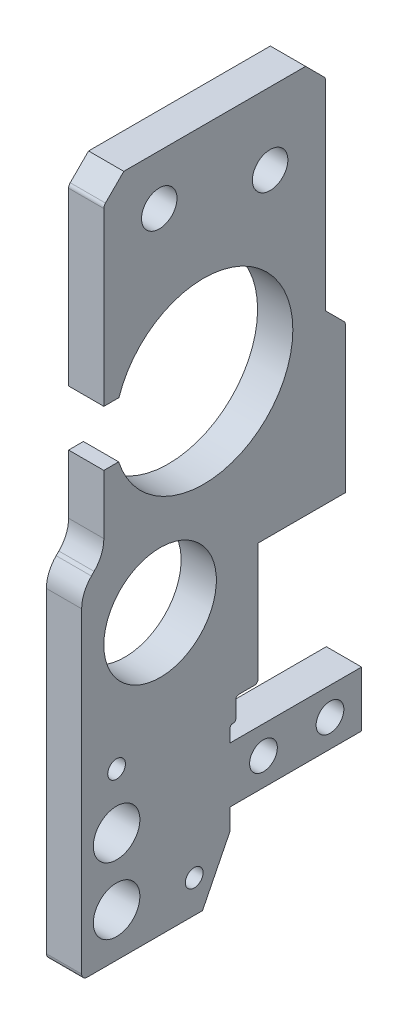
SolidWorks part; units mm, degrees
material "6061 Alloy"
ref_plane "Front Plane" through (0, 0, 0) normal (0, 0, 1) x (1, 0, 0)
ref_plane "Top Plane" through (0, 0, 0) normal (0, 1, 0) x (1, 0, 0)
ref_plane "Right Plane" through (0, 0, 0) normal (1, 0, 0) x (0, 0, -1)
sketch "Sketch1" plane through (0, 0, 0) normal (1, 0, 0) x (0, 0, -1)
  line L2 (0, 0) -> (0, 30.275)
  line L3 (0, 30.275) -> (2, 32.275)
  line L4 (2, 32.275) -> (2, 61.31)
  line L5 (2, 61.31) -> (22, 61.31)
  line L7 (23.8, 26.21) -> (15.9, 26.21)
  line L8 (13.4, 13.26) -> (13.4, 11.86)
  line L9 (13.4, 11.86) -> (25.25, 11.86)
  line L10 (25.25, 11.86) -> (25.25, 6.86)
  line L11 (25.25, 6.86) -> (13.4, 6.86)
  line L12 (13.4, 6.86) -> (13.4, 0)
  line L13 (13.4, 0) -> (0, 0)
  line L14 (-6.9356, -4) -> (62.4069, -4) construction
  line L15 (7.075, 30.275) -> (0, 30.275) construction
  line L16 (7.075, 20.125) -> (0, 20.125) construction
  line L17 (2, 18.125) -> (2, 32.275) construction
  line L18 (13.4, 13.26) -> (13.9, 13.26)
  line L19 (15.9, 15.26) -> (15.9, 26.21)
  line L23 (22, 61.31) -> (22, 41.31)
  line L24 (22, 41.31) -> (23.8, 41.31)
  line L25 (23.8, 41.31) -> (23.8, 26.21)
  line L29 (15.9, 15.26) -> (13.9, 15.26)
  line L30 (13.9, 13.26) -> (13.9, 15.26)
  circle A0 centre (7.075, 25.2) radius 5.075
  circle A1 centre (7, 56.81) radius 1.6
  circle A2 centre (17, 54.81) radius 1.6
  circle A3 centre (22.4, 9.36) radius 1.25
  circle A4 centre (16.4, 9.36) radius 1.25
  circle A5 centre (3.15, 3.95) radius 2.1
  circle A6 centre (3.15, 9.95) radius 2.1
  circle A7 centre (22.4, 9.36) radius 2.85 construction
  circle A8 centre (16.4, 9.36) radius 2.85 construction
  circle A9 centre (10.15, 2.95) radius 0.8
  circle A10 centre (3.15, 14.95) radius 0.8
  dimension "D11" = 10.15
  dimension "D13" = 3.2
  dimension "D17" = 5
  dimension "D21" = 2.5
  dimension "D29" = 7.9
  dimension "D33" = 4.2
  dimension "D34" = 5.7
  dimension "D35" = 2
  dimension "D36" = 1.6
  dimension "D3" = 10.86
  dimension "D4" = 5
  dimension "D5" = 14.35
  dimension "D6" = 11.85
  dimension "D7" = 61.31
  dimension "D8" = 4
  dimension "D9" = 2
  dimension "D10" = 2
  dimension "D12" = 29.2
  dimension "D14" = 6.5
  dimension "D15" = 4.5
  dimension "D16" = 5
  dimension "D18" = 6
  dimension "D19" = 1.45
  dimension "D20" = 2.5
  dimension "D22" = 1.4
  dimension "D23" = 7
  dimension "D24" = 20
  dimension "D25" = 2.95
  dimension "D26" = 1.8
  dimension "D27" = 20
  dimension "D28" = 2
  dimension "D30" = 6
  dimension "D31" = 3.95
  dimension "D32" = 3.15
  dimension "D38" = 12
extrude "Boss-Extrude1" add sketch "Sketch1" along normal blind 3.18
chamfer "Chamfer1" distance 2.5 angle 63.43 1 edges at (1.59, 0, -13.4) first distance on face at (1.59, 0, -6.7)
fillet "Fillet1" [suppressed] radius 1
sketch "Sketch3" [suppressed] plane through (0, 0, 0) normal (1, 0, 0) x (0, 0, -1)
  line L1 (-17.4326, 42.2448) -> (-6.9749, 46.4147) construction
  line L2 (-6.9749, 46.4147) -> (-8.5925, 35.2732) construction
  line L3 (-8.5925, 35.2732) -> (-17.4326, 42.2448) construction
  line L4 (-2, 61.31) -> (-2, 32.2) construction
  circle A0 centre (-11, 41.3109) radius 5
  circle A2 centre (-11, 41.3109) radius 6.5 construction
  circle A3 centre (-6.9749, 46.4147) radius 1.2 construction
  circle A4 centre (-8.5925, 35.2732) radius 1.2 construction
  circle A5 centre (-17.4326, 42.2448) radius 1.2 construction
  circle A6 centre (-7, 25.2) radius 5 construction
  dimension "D1" = 10
  dimension "D3" = 16.6
  dimension "D4" = 13
  dimension "D5" = 2.4
  dimension "D2" = 9
hole_wizard "CSK for M2 Flat Head Machine Screw1" [suppressed] positions "Sketch6" profile "Sketch7" countersink size "M2" standard "ANSI Metric"
sketch "Sketch6" plane through (0, 0, 0) normal (-1, 0, 0) x (0, 0, 1)
  point P0 (-6.9749, 46.4147)
  point P3 (-17.4326, 42.2448)
  point P6 (-8.5925, 35.2732)
sketch "Sketch7" plane through (0, 46.4147, -6.9749) normal (0, 1, 0) x (0, 0, 1)
  line L0 (0, 0) -> (0, 4.23)
  line L1 (0, 4.23) -> (1.2, 3.509)
  line L2 (1.2, 3.509) -> (1.2, 1)
  line L3 (1.2, 1) -> (2.2, 0)
  line L5 (2.2, 0) -> (0, 0)
  line L6 (-1.2, 1) -> (-2.2, 0) construction
  line L10 (0, 4.23) -> (-1.2, 3.509) construction
  line L11 (0, -6.35) -> (0, 107.95) construction
  dimension "Hole Dia." = 2.4
  dimension "Hole Depth" = 4.23
  dimension "Near C'Sink Dia." = 4.4
  dimension "Near C'Sink Angle" = 90
  dimension "Drill Angle" = 118
extrude "Cut-Extrude4" [suppressed] cut sketch "Sketch3" against normal through all
fillet "Fillet2" radius 3 2 edges at (1.59, 30.275, 0) (1.59, 32.275, -2)
fillet "Chamfer2" radius 1.8 3 edges at (1.59, 61.31, -22) (1.59, 61.31, -2) (1.59, 41.31, -23.8) profile chamfer
fillet "Fillet4" radius 0.5 5 edges at (1.59, 59.51, -2) (1.59, 59.51, -22) (1.59, 39.51, -23.8) (1.59, 0, 0) (1.59, 4.9989, -13.4)
fillet "Fillet6" [suppressed] radius 0.3
sketch "BallRef" [suppressed] plane through (0, 0, 0) normal (-1, 0, 0) x (0, 0, 1)
  line L0 (-31.524, -18.06) -> (65.6624, -18.06) construction
  line L1 (-0.75, 25.2) -> (-0.75, 21.8885) construction
  line L2 (-0.75, 21.8885) -> (31.3703, 21.8885) construction
  line L3 (31.3703, 3.35) -> (31.3703, 21.8885) construction
  line L4 (1.092, -18.06) -> (-13.908, -3.06) construction
  line L5 (-13.908, -3.06) -> (-13.908, -18.06) construction
  line L6 (-13.908, -18.06) -> (1.092, -18.06) construction
  circle A0 centre (-7, 25.2) radius 6.25 construction
  circle A1 centre (9.9603, 3.35) radius 21.41 construction
  dimension "D1" = 12.5
  dimension "D2" = 42.82
  dimension "D3" = 43.26
  dimension "D4" = 45
  dimension "D5" = 15
fillet "Fillet7" radius 0.2 2 edges at (1.59, 13.26, -13.4) (1.59, 13.26, -13.9)
hole_wizard "M3x0.5 Tapped Hole1" positions "Sketch9" profile "Sketch10" tap size "M3x0.5" standard "ANSI Metric" end condition through all
sketch "Sketch9" plane through (3.18, 0, 0) normal (1, 0, 0) x (0, 0, -1)
  point P0 (16.4, 9.36)
  point P3 (22.4, 9.36)
sketch "Sketch10" plane through (3.18, 9.36, -16.4) normal (0, 1, 0) x (0, 0, -1)
  line L0 (0, 0) -> (0, 3.18)
  line L1 (0, 3.18) -> (1.25, 3.18)
  line L2 (1.25, 3.18) -> (1.25, 0)
  line L5 (1.25, 0) -> (0, 0)
  line L11 (0, -6.35) -> (0, 107.95) construction
  dimension "Thru Tap Drill Dia." = 2.5
  dimension "Thru Tap Drill Depth" = 3.18
hole_wizard "M2 Tapped Hole1" positions "3DSketch1" profile "Sketch12" tap size "M2" standard "AS" end condition through all
sketch3d "3DSketch1"
  line L0 (3.18, 14.95, -3.15) -> (0, 14.95, -3.15) construction
  line L1 (3.18, 2.95, -10.15) -> (0, 2.95, -10.15) construction
  point P0 (0, 14.95, -3.15)
  point P4 (0, 2.95, -10.15)
sketch "Sketch12" plane through (0, 14.95, -3.15) normal (0, 1, 0) x (0, 0, 1)
  line L0 (0, 0) -> (0, 3.18)
  line L1 (0, 3.18) -> (0.8, 3.18)
  line L2 (0.8, 3.18) -> (0.8, 0)
  line L5 (0.8, 0) -> (0, 0)
  line L11 (0, -6.35) -> (0, 107.95) construction
  dimension "Thru Tap Drill Dia." = 1.6
  dimension "Thru Tap Drill Depth" = 3.18
cosmetic thread "Hole Thread3" parameters "D2"=2
cosmetic thread "Hole Thread4" parameters "D2"=2
fillet "Fillet8" radius 0.3 2 edges at (1.59, 15.26, -15.9) (1.59, 15.26, -13.9)
sketch "Sketch13" plane through (3.18, 0, 0) normal (1, 0, 0) x (0, 0, -1)
  line L1 (2, 59.3029) -> (2, 33.5176) construction
  line L2 (2, 43.8466) -> (2, 38.8466)
  line L3 (2, 43.8466) -> (3.3601, 43.8466)
  line L5 (3.3362, 38.8466) -> (2, 38.8466)
  arc A0 (3.3362, 38.8466) -> (3.3601, 43.8466) centre (11, 41.31) ccw
extrude "Cut-Extrude5" cut sketch "Sketch13" against normal blind 4
equation "\"7.5.00mm\"=5"
